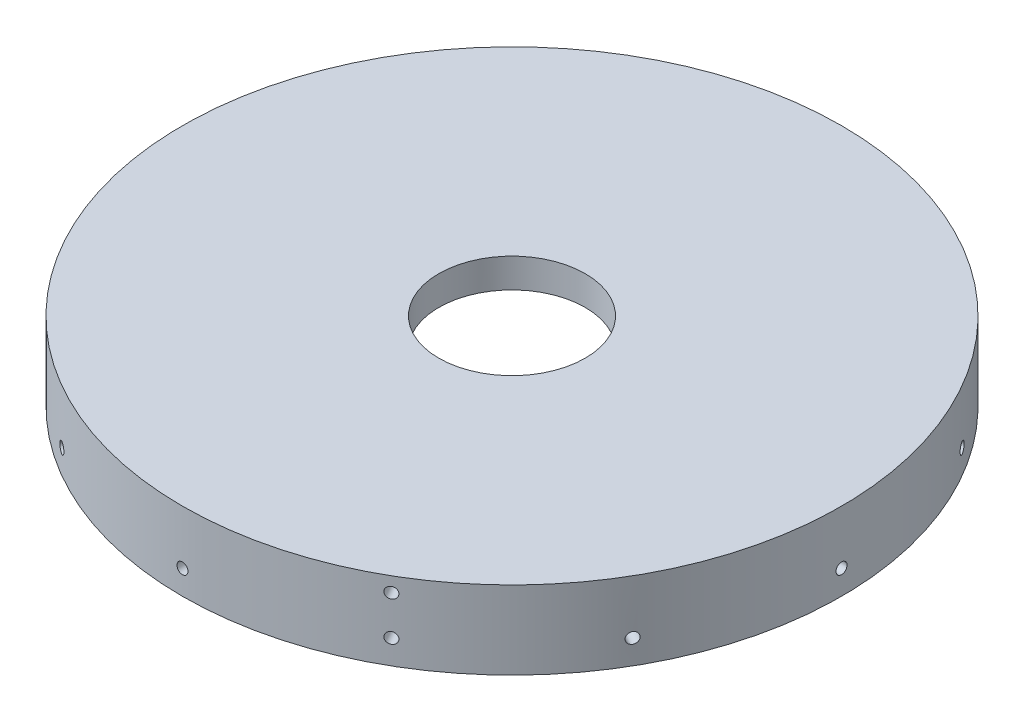
SolidWorks part; units mm, degrees
material "6061-T6 (SS)"
ref_plane "Front Plane" through (0, 0, 0) normal (0, 0, 1) x (1, 0, 0)
ref_plane "Top Plane" through (0, 0, 0) normal (0, 1, 0) x (1, 0, 0)
ref_plane "Right Plane" through (0, 0, 0) normal (1, 0, 0) x (0, 0, -1)
sketch "Sketch1" plane through (0, 0, 0) normal (0, 1, 0) x (1, 0, 0)
  circle A0 centre (0, 0) radius 85.725
  dimension "D1" = 171.45
extrude "Boss-Extrude1" add sketch "Sketch1" along normal mid plane 7.62
sketch "Sketch2" plane through (0, -3.81, 0) normal (0, -1, 0) x (1, 0, 0)
  circle A0 centre (0, 0) radius 19.05
  dimension "D1" = 38.1
extrude "Cut-Extrude1" cut sketch "Sketch2" against normal up to surface (7.62 mm away) up to face at (0, 3.81, 85.725)
sketch "Sketch4" plane through (0, -3.81, 0) normal (0, -1, 0) x (1, 0, 0)
  circle A0 centre (0, 0) radius 85.725
  circle A1 centre (0, 0) radius 79.375
  dimension "D1" = 171.45
  dimension "D2" = 158.75
extrude "Boss-Extrude2" add sketch "Sketch4" along normal blind 12.7
ref_plane "Plane1" through (-85.725, 0, 0) normal (-1, 0, 0) x (0, 0, 1)
sketch "Sketch3" plane through (-85.725, 0, 0) normal (-1, 0, 0) x (0, 0, 1)
  circle A0 centre (0, 0) radius 1.4351
  dimension "D1" = 2.8702
extrude "Cut-Extrude2" cut sketch "Sketch3" against normal blind 15.24
pattern_circular "CirPattern1" count 3 over 360 about axis through (0, 3.81, 0) along (0, -1, 0) of "Cut-Extrude2" reverse direction yes
sketch "Sketch5" plane through (-85.725, 0, 0) normal (-1, 0, 0) x (0, 0, 1)
  line L0 (0, -11.176) -> (0, 11.176) construction
  line L1 (-79.375, -16.51) -> (79.375, -16.51) construction
  circle A0 centre (0, -10.1828) radius 1.4351
  dimension "D1" = 2.8702
  dimension "D2" = 6.3272
extrude "Cut-Extrude3" cut sketch "Sketch5" against normal blind 17.018
pattern_circular "CirPattern2" count 12 over 360 about axis through (0, 3.81, 0) along (0, -1, 0) of "Cut-Extrude3"
